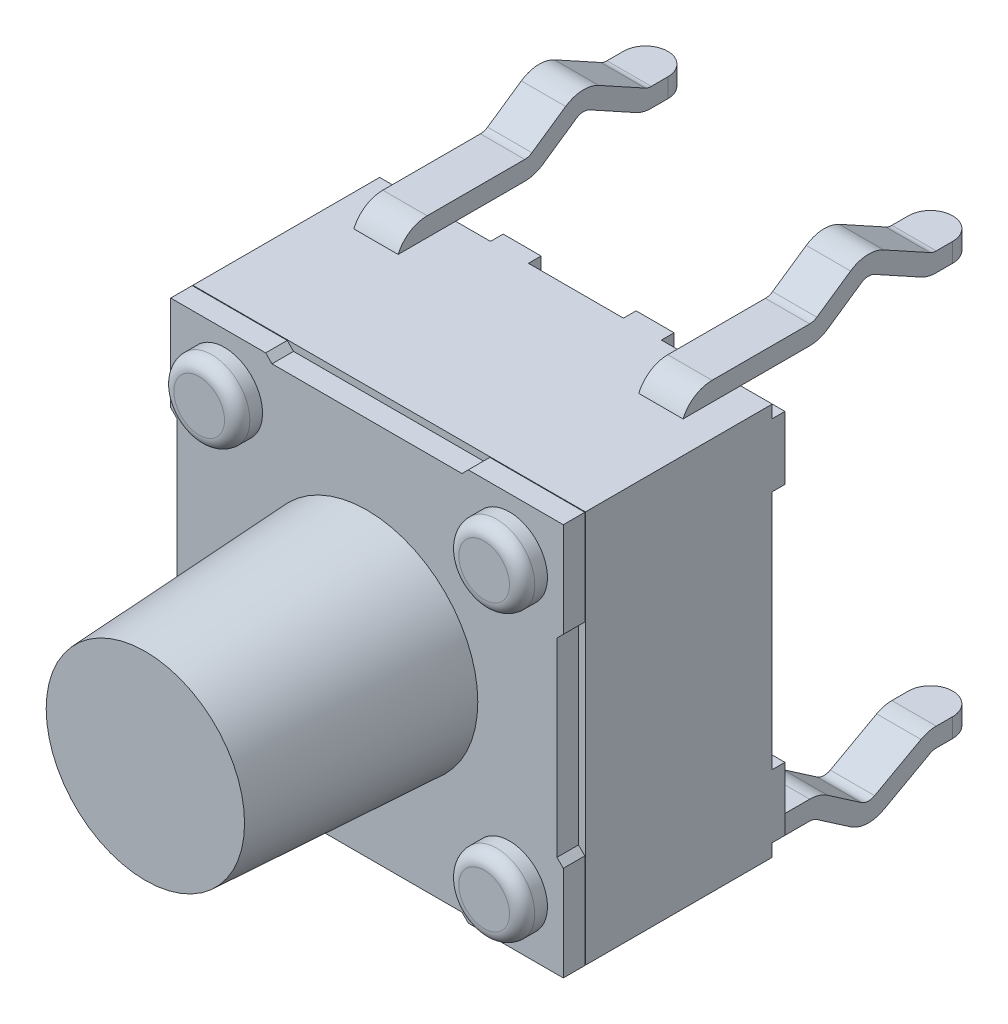
SolidWorks part; units mm, degrees
ref_plane "Спереди" through (0, 0, 0) normal (0, 0, 1) x (1, 0, 0)
ref_plane "Сверху" through (0, 0, 0) normal (0, 1, 0) x (1, 0, 0)
ref_plane "Справа" through (0, 0, 0) normal (1, 0, 0) x (0, 0, -1)
sketch "Эскиз1" plane through (0, 0, 0) normal (0, 0, 1) x (1, 0, 0)
  point P0 (-2.25, -3.25)
  point P1 (-2.25, 3.25)
  dimension "D1" = 3.25
  dimension "D2" = 3.25
  dimension "D3" = 2.25
ref_plane "Плоскость траектории вывода" through (-2.25, 0, 0) normal (1, 0, 0) x (0, 0, -1)
sketch "Траектория выводов" plane through (-2.25, 0, 0) normal (1, 0, 0) x (0, 0, -1)
  line L0 (0, 3.25) -> (-1, 3.25)
  line L1 (-1, 3.25) -> (-1, -3.25)
  line L2 (55, 0) -> (-55, 0) construction
  line L3 (2.8, -3.25) -> (3.5, -3.25)
  line L4 (1.8, -3.8) -> (2.8, -3.25)
  line L5 (0, 3.25) -> (1, 3.25)
  line L6 (1, 3.25) -> (1.8, 3.8)
  line L7 (1.8, 3.8) -> (2.8, 3.25)
  line L8 (1, -3.25) -> (1.8, -3.8)
  line L9 (0, -3.25) -> (1, -3.25)
  line L10 (2.8, 3.25) -> (3.5, 3.25)
  line L11 (0, -3.25) -> (-1, -3.25)
  point P3 (0, 0)
  point P5 (0, 0)
  point P6 (0, 0)
  point P13 (0, 0)
  point P19 (0, 0)
  dimension "D1" = 1
  dimension "D2" = 1
  dimension "D3" = 0.8
  dimension "D4" = 1
  dimension "D5" = 3.8
  dimension "D6" = 0.7
extrude "Выводы 1-2" add sketch "Траектория выводов" along normal blind 0.35 and the other way blind 0.35 thin thin type mid plane wall 0.3
fillet "Скругление2" radius 0.35 4 edges at (-1.9, -3.25, -3.5) (-2.6, -3.25, -3.5) (-1.9, 3.25, -3.5) (-2.6, 3.25, -3.5)
mirror "Зеркальное отражение4" about plane through (0, 0, 0) normal (1, 0, 0) of bodies 101
sketch "Эскиз4" plane through (0, 0, 0) normal (0, 0, 1) x (1, 0, 0)
  line L1 (-3.1, -3.1) -> (3.1, -3.1)
  line L2 (-3.1, -3.1) -> (-3.1, 3.1)
  line L3 (-3.1, 3.1) -> (3.1, 3.1)
  line L4 (3.1, -3.1) -> (3.1, 3.1)
  line L5 (-3.1, -3.1) -> (3.1, 3.1) construction
  line L6 (-3.1, 3.1) -> (3.1, -3.1) construction
  point P0 (0, 0)
  dimension "D1" = 6.2
  dimension "D2" = 6.2
extrude "Корпус" add sketch "Эскиз4" along normal blind 2.95 from offset 0.2
sketch "Эскиз9" plane through (0, 0, 0) normal (0, 0, 1) x (1, 0, 0)
  line L0 (-0.75, -3.1) -> (-0.75, 3.1)
  line L1 (-3.1, -3.1) -> (3.1, -3.1) construction
  line L2 (-0.75, 3.1) -> (-1.35, 3.1)
  line L3 (-3.1, 3.1) -> (3.1, 3.1) construction
  line L4 (-1.35, 3.1) -> (-1.35, 2.9)
  line L5 (-1.35, 2.9) -> (-2.9, 2.9)
  line L6 (-3.1, 3.1) -> (3.1, -3.1) construction
  line L7 (-2.9, 2.9) -> (-3.1, 2.9)
  line L8 (-3.1, -3.1) -> (-3.1, 3.1) construction
  line L9 (-3.1, 2.9) -> (-3.1, 1.9)
  line L10 (-3.1, 1.9) -> (-1.35, 1.9)
  line L11 (-1.35, 1.9) -> (-1.35, -1.9)
  line L12 (-1.35, -1.9) -> (-3.1, -1.9)
  line L13 (-3.1, -1.9) -> (-3.1, -2.9)
  line L14 (-3.1, -2.9) -> (-1.35, -2.9)
  line L15 (-1.35, -2.9) -> (-1.35, -3.1)
  line L16 (-1.35, -3.1) -> (-0.75, -3.1)
  line L17 (0, -2.5575) -> (0, 2.5575) construction
  line L18 (1.35, -3.1) -> (0.75, -3.1)
  line L19 (1.35, -2.9) -> (1.35, -3.1)
  line L20 (3.1, -2.9) -> (1.35, -2.9)
  line L21 (3.1, -1.9) -> (3.1, -2.9)
  line L22 (1.35, -1.9) -> (3.1, -1.9)
  line L23 (1.35, 1.9) -> (1.35, -1.9)
  line L24 (3.1, 1.9) -> (1.35, 1.9)
  line L25 (3.1, 2.9) -> (3.1, 1.9)
  line L26 (2.9, 2.9) -> (3.1, 2.9)
  line L27 (1.35, 2.9) -> (2.9, 2.9)
  line L28 (1.35, 3.1) -> (1.35, 2.9)
  line L29 (0.75, 3.1) -> (1.35, 3.1)
  line L30 (0.75, -3.1) -> (0.75, 3.1)
  dimension "D1" = 0.75
  dimension "D2" = 0.6
  dimension "D3" = 1
  dimension "D4" = 0.2
  dimension "D5" = 0.2
  dimension "D6" = 1
extrude "Рельеф снизу" add sketch "Эскиз9" along normal blind 0.3
sketch "Эскиз5" plane through (0, 0, 3.15) normal (0, 0, 1) x (1, 0, 0)
  line L0 (-3.1, 3.1) -> (-3.1, -3.1) construction
  line L1 (0, 3) -> (1.5, 3)
  line L2 (1.5, 3) -> (1.6, 3.1)
  line L3 (-3, 0) -> (-3, 1.5)
  line L4 (-3, 1.5) -> (-3.1, 1.6)
  line L5 (-3.1, 1.6) -> (-3.1, 3.1)
  line L6 (3.1, 3.1) -> (-3.1, 3.1) construction
  line L7 (-3.1, 3.1) -> (-1.6, 3.1)
  line L8 (-1.6, 3.1) -> (-1.5, 3)
  line L9 (-1.5, 3) -> (0, 3)
  line L10 (1.6, 3.1) -> (3.1, 3.1)
  line L12 (3.1, 3.1) -> (3.1, 1.6)
  line L13 (3.1, 1.6) -> (3, 1.5)
  line L14 (3, 1.5) -> (3, 0)
  line L15 (3, 0) -> (3, -1.5)
  line L16 (3, -1.5) -> (3.1, -1.6)
  line L17 (3.1, -1.6) -> (3.1, -3.1)
  line L18 (3.1, -3.1) -> (1.6, -3.1)
  line L19 (1.6, -3.1) -> (1.5, -3)
  line L20 (1.5, -3) -> (0, -3)
  line L21 (0, -3) -> (-1.5, -3)
  line L22 (-1.5, -3) -> (-1.6, -3.1)
  line L23 (-1.6, -3.1) -> (-3.1, -3.1)
  line L24 (-3.1, -3.1) -> (-3.1, -1.6)
  line L25 (-3.1, -1.6) -> (-3, -1.5)
  line L26 (-3, -1.5) -> (-3, 0)
  point P37 (0, 0)
  dimension "D1" = 3
  dimension "D2" = 3
  dimension "D3" = 1.5
  dimension "D4" = 1.5
  dimension "D5" = 0.1
  dimension "D6" = 0.1
  dimension "D7" = 4
extrude "Крышка" add sketch "Эскиз5" along normal blind 0.34 from offset 0.01 separate body
sketch "Эскиз6" plane through (0, 0, 3.5) normal (0, 0, 1) x (1, 0, 0)
  circle A0 centre (-2.25, -2.25) radius 0.6
  circle A1 centre (-2.25, 2.25) radius 0.6
  circle A2 centre (2.25, 2.25) radius 0.6
  circle A3 centre (2.25, -2.25) radius 0.6
  point P12 (0, 0)
  dimension "D3" = 1.2
  dimension "D1" = 2.25
  dimension "D2" = 2.25
  dimension "D4" = 4
extrude "Заклепки" add sketch "Эскиз6" along normal blind 0.4
fillet "Скругление3" radius 0.2 4 edges at (2.85, -2.25, 3.9) (2.85, 2.25, 3.9) (-1.65, 2.25, 3.9) (-1.65, -2.25, 3.9)
sketch "Эскиз7" plane through (0, 0, 3.5) normal (0, 0, 1) x (1, 0, 0)
  circle A0 centre (0, 0) radius 1.75
  dimension "D1" = 3.5
extrude "Толкатель" add sketch "Эскиз7" along normal blind 3.5 draft 3
